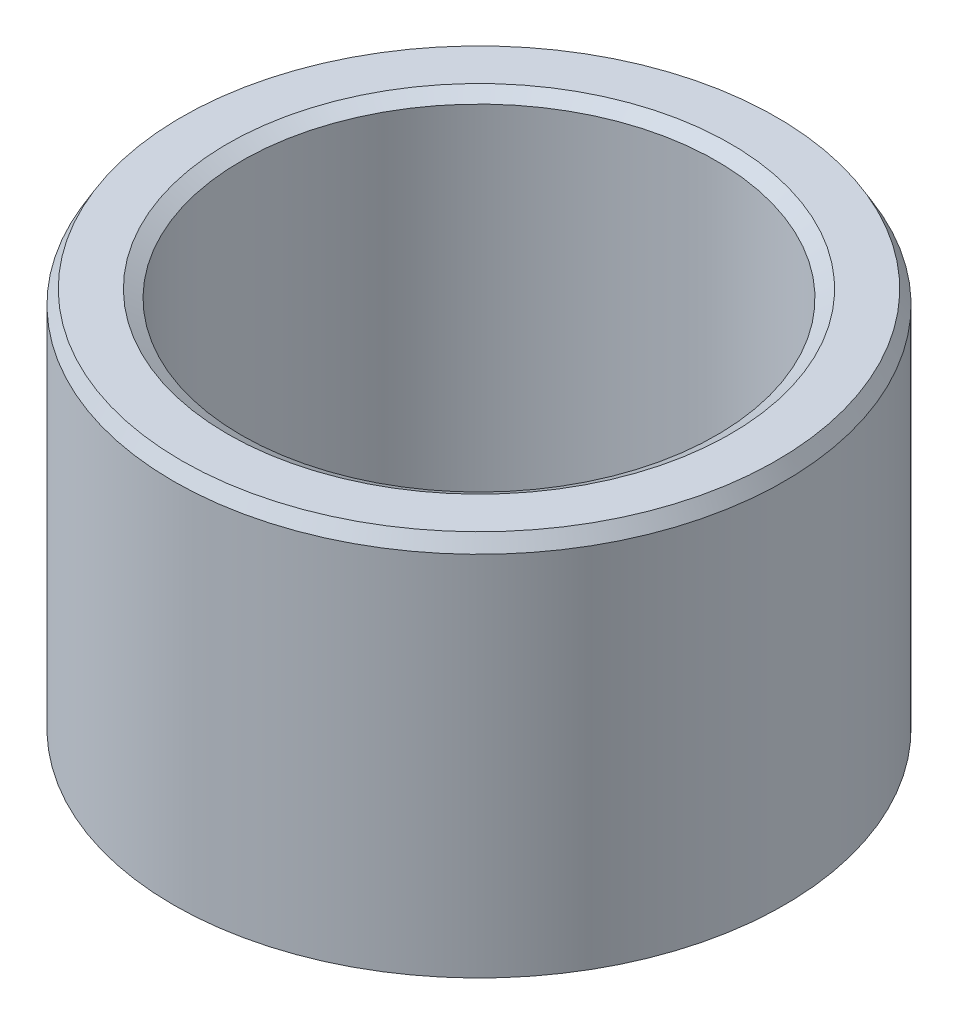
SolidWorks part; units mm, degrees
ref_plane "Front Plane" through (0, 0, 0) normal (0, 0, 1) x (1, 0, 0)
ref_plane "Top Plane" through (0, 0, 0) normal (0, 1, 0) x (1, 0, 0)
ref_plane "Right Plane" through (0, 0, 0) normal (1, 0, 0) x (0, 0, -1)
sketch "Sketch1" plane through (0, 0, 0) normal (0, 1, 0) x (1, 0, 0)
  circle A0 centre (0, 0) radius 25
  dimension "SLEEVE_OD" = 50
extrude "Boss-Extrude1" add sketch "Sketch1" along normal blind 31.816
sketch "Sketch2" plane through (0, 0, 0) normal (0, 1, 0) x (1, 0, 0)
  circle A0 centre (0, 0) radius 19.4408
  dimension "BORE_D" = 38.8816
extrude "Cut-Extrude1" cut sketch "Sketch2" along normal through all
chamfer "Chamfer1" distance 1.1355 angle 30 4 edges at (0, 31.816, 19.4408) (0, 0, 19.4408) (0, 0, 25) (0, 31.816, 25) first distance on face at (0, 31.816, 19.4408) first distance on face at (0, 0, 19.4408) first distance on face at (0, 31.816, 25)
